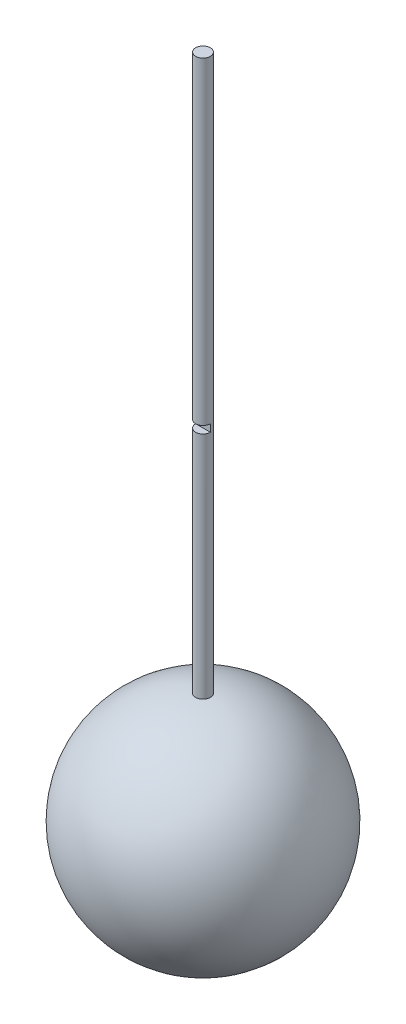
SolidWorks part; units mm, degrees
ref_plane "Alzado" through (0, 0, 0) normal (0, 0, 1) x (1, 0, 0)
ref_plane "Planta" through (0, 0, 0) normal (0, 1, 0) x (1, 0, 0)
ref_plane "Vista lateral" through (0, 0, 0) normal (1, 0, 0) x (0, 0, -1)
sketch "Croquis2" plane through (0, 0, 0) normal (0, 0, 1) x (1, 0, 0)
  line L0 (0, 15) -> (0, 13.2921)
  line L2 (0, -13.2921) -> (0, -15)
  arc A0 (0, 15) -> (0, -15) centre (0, 0) ccw
  arc A1 (0, 13.2921) -> (0, -13.2921) centre (0, 0) ccw
  dimension "D1" = 30
revolve "Revolución1" add sketch "Croquis2" angle 360 about L0
sketch "Croquis3" plane through (0, 0, 0) normal (0, 1, 0) x (1, 0, 0)
  circle A0 centre (0, 0) radius 1
  dimension "D1" = 2
extrude "Saliente-Extruir1" add sketch "Croquis3" along normal blind 90
sketch "Croquis4" plane through (0, 0, 0) normal (1, 0, 0) x (0, 0, -1)
  line L0 (-4.1397, 47) -> (0, 47)
  line L1 (0, 47) -> (0, 46)
  line L2 (0, 46) -> (-4.1397, 46)
  line L3 (-4.1397, 46) -> (-4.1397, 47)
  line L4 (1, 90) -> (-1, 90) construction
  dimension "D1" = 43
extrude "Cortar-Extruir1" cut sketch "Croquis4" against normal blind 10 and the other way blind 10
